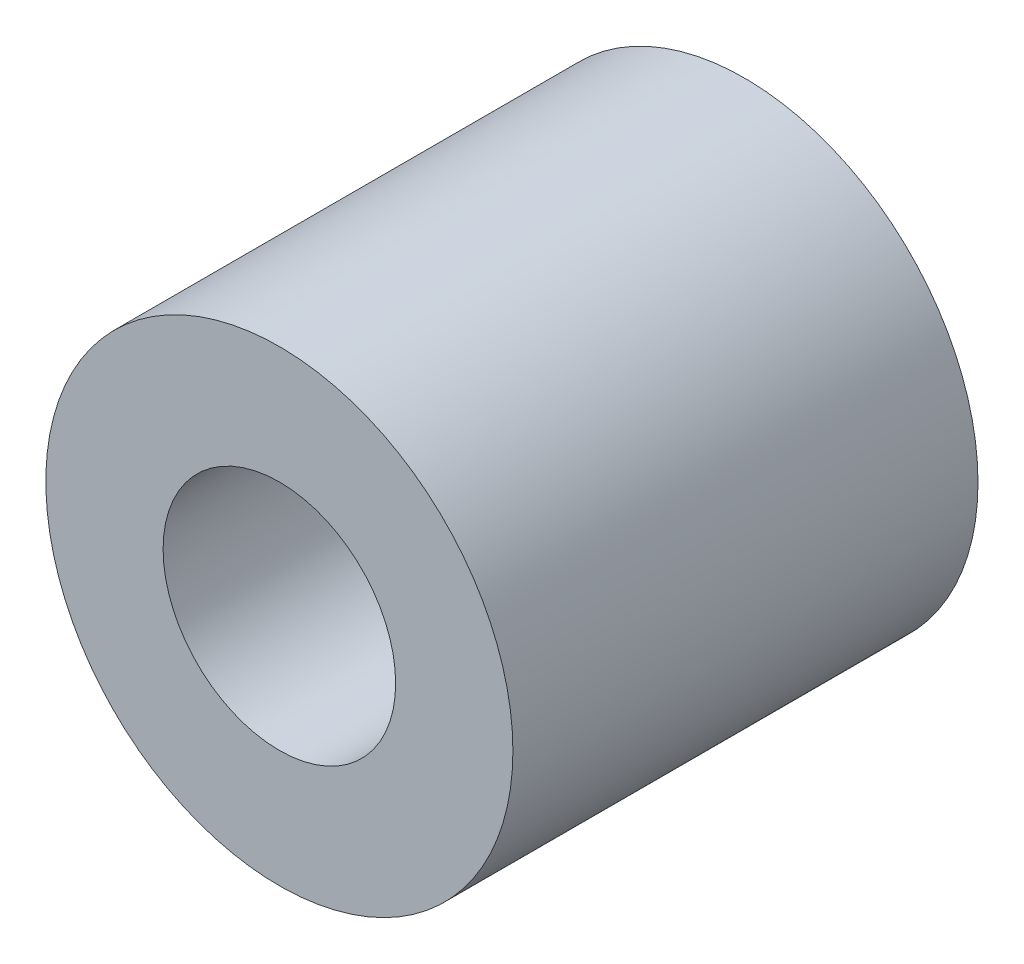
SolidWorks part; units mm, degrees
ref_plane "Front Plane" through (0, 0, 0) normal (0, 0, 1) x (1, 0, 0)
ref_plane "Top Plane" through (0, 0, 0) normal (0, 1, 0) x (1, 0, 0)
ref_plane "Right Plane" through (0, 0, 0) normal (1, 0, 0) x (0, 0, -1)
sketch "Sketch1" plane through (0, 0, 0) normal (0, 0, 1) x (1, 0, 0)
  circle A0 centre (0, 0) radius 6.0255 construction
  circle A1 centre (0, 0) radius 3 construction
  dimension "ID" = 6
  dimension "OD" = 12.051
sketch "Sketch2" plane through (0, 0, 0) normal (1, 0, 0) x (0, 0, -1)
  line L0 (-6, 0) -> (6, 0) construction
  dimension "Length" = 12
sketch "Sketch3" plane through (0, 0, 0) normal (0, 0, 1) x (1, 0, 0)
  circle A0 centre (0, 0) radius 3 construction
  circle A1 centre (0, 0) radius 6.0255 construction
  circle A2 centre (0, 0) radius 3
  circle A3 centre (0, 0) radius 6.0255
extrude "Boss-Extrude1" add sketch "Sketch3" along normal up to vertex (-6 mm away) and the other way up to vertex (-6 mm away) up to point (0, 0, -6) other way up to point (0, 0, 6)
ref_axis "Center Axis 1" through (0, 0, 1.65) along (0, 0, -1)
